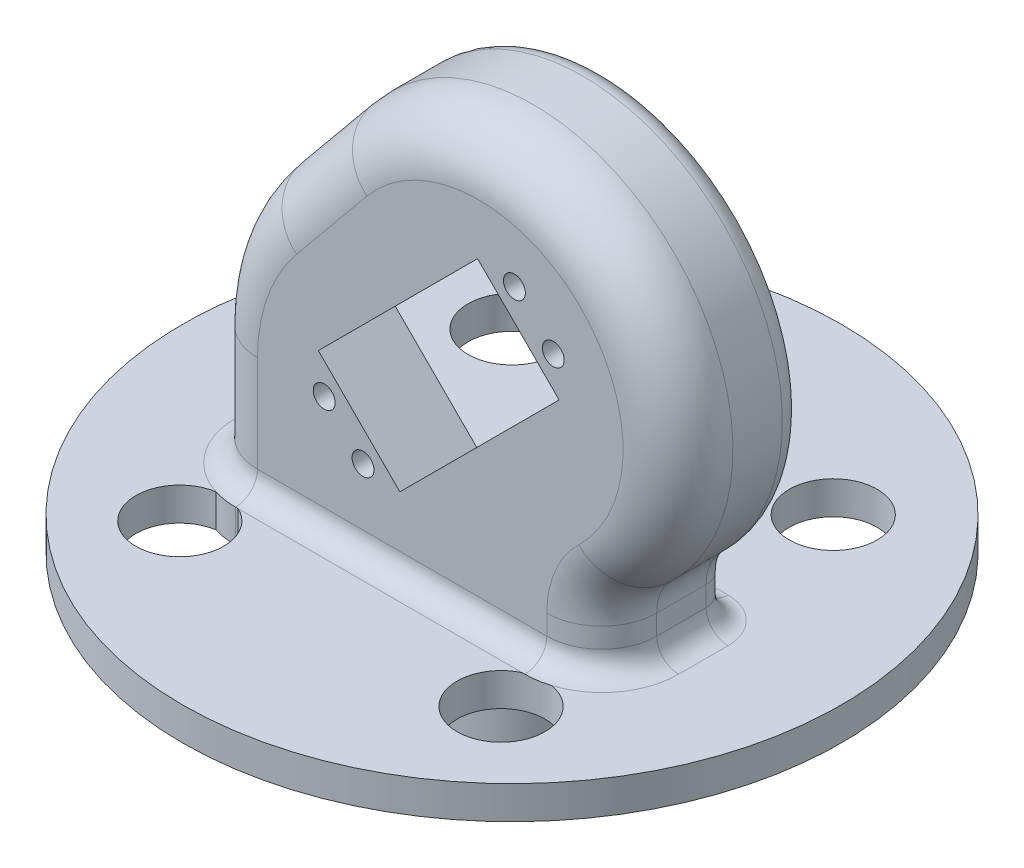
SolidWorks part; units mm, degrees
ref_plane "Front Plane" through (0, 0, 0) normal (0, 0, 1) x (1, 0, 0)
ref_plane "Top Plane" through (0, 0, 0) normal (0, 1, 0) x (1, 0, 0)
ref_plane "Right Plane" through (0, 0, 0) normal (1, 0, 0) x (0, 0, -1)
sketch "Sketch1" plane through (0, 0, 0) normal (0, 1, 0) x (1, 0, 0)
  line L0 (0, -7.25) -> (0, 7.25)
  circle A0 centre (0, 0) radius 60
  circle A1 centre (0, 7.25) radius 1.5
  circle A2 centre (0, -7.25) radius 1.5
  point P6 (0, 0)
  dimension "D2" = 120
  dimension "D3" = 3
  dimension "D1" = 14.5
extrude "Boss-Extrude2" add sketch "Sketch1" along normal blind 4 contours A0 A2 A1 region at (-58.3029, 0, 0)
sketch "Sketch8" plane through (0, 0, 0) normal (0, 0, 1) x (1, 0, 0)
  line L0 (-30.34, 4) -> (30.34, 4)
  line L1 (-30.34, 4) -> (-30.34, 25.5686)
  line L2 (60, 4) -> (-60, 4) construction
  line L3 (30.34, 4) -> (30.34, 11.64)
  line L4 (-22.3212, 47.945) -> (-9.5029, 63.533)
  arc A0 (30.34, 11.64) -> (34.9356, 22.445) centre (45.34, 11.64) cw
  arc A1 (34.9356, 22.445) -> (-9.5029, 63.533) centre (13.91, 44.28) ccw
  arc A2 (-30.34, 25.5686) -> (-22.3212, 47.945) centre (4.89, 25.5686) cw
  circle A3 centre (13.91, 44.28) radius 9
  point P2 (0, 4)
  dimension "D3" = 15
  dimension "D4" = 35.23
  dimension "D5" = 13.91
  dimension "D6" = 18
  dimension "D1" = 60.68
  dimension "D2" = 7.64
  dimension "D7" = 40.28
extrude "Boss-Extrude3" add sketch "Sketch8" along normal blind 14 from offset 6 contours A3 | A2 L1 L0 L3 A0 A1 L4 A3 region at (6.5155, 35.8962, 0) region at (13.91, 44.28, 0)
sketch "Sketch9" plane through (0, 0, 0) normal (0, -1, 0) x (1, 0, 0)
  arc A0 (0.8292, 6) -> (-0.8292, 6) centre (0, 7.25) ccw construction
  circle A1 centre (0, -7.25) radius 1.5
  circle A2 centre (0, -7.25) radius 1.5
  arc A3 (0.8292, 6) -> (-0.8292, 6) centre (0, 7.25) ccw
  circle M3 centre (0, -7.25) radius 1.5
  circle M4 centre (0, 7.25) radius 1.5
  dimension "D1" = 0
extrude "Boss-Extrude4" add sketch "Sketch9" against normal up to surface (4 mm away) contours M3 | M4 | A2 region at (0, 0, -7.25) region at (0, 0, 7.25) up to face at (0, 4, -5.75)
sketch "Sketch21" plane through (0, 0, 20) normal (0, 0, 1) x (1, 0, 0)
  line L1 (60, 4) -> (-60, 4) construction
  line L2 (36.34, 11.64) -> (36.34, 4)
  line L3 (36.34, 11.64) -> (36.34, 4)
  line L4 (-30.34, 4) -> (-27.34, 4)
  line L5 (-36.34, 4) -> (-27.34, 4)
  line L6 (30.34, 4) -> (36.34, 4)
  line L9 (-26.9556, 51.7559) -> (-14.1373, 67.3439)
  line L10 (-36.34, 4) -> (-36.34, 25.5686)
  line L11 (-26.9556, 51.7559) -> (-14.1373, 67.3439)
  line L12 (-36.34, 4) -> (-36.34, 25.5686)
  line L14 (33.34, 11.64) -> (33.34, 4)
  line L15 (-24.6384, 49.8505) -> (-11.8201, 65.4384)
  line L16 (-33.34, 4) -> (-33.34, 25.5686)
  line L17 (33.34, 11.64) -> (33.34, 4) construction
  line L18 (-24.6384, 49.8505) -> (-11.8201, 65.4384) construction
  line L19 (-33.34, 4) -> (-33.34, 25.5686) construction
  arc A2 (-9.5029, 63.533) -> (-27.34, 4) centre (72.6291, 6.4862) ccw
  arc A3 (39.0973, 18.123) -> (36.34, 11.64) centre (45.34, 11.64) ccw
  arc A4 (39.0973, 18.123) -> (36.34, 11.64) centre (45.34, 11.64) ccw
  arc A7 (39.0973, 18.123) -> (-14.1373, 67.3439) centre (13.91, 44.28) ccw
  arc A8 (-26.9556, 51.7559) -> (-36.34, 25.5686) centre (4.89, 25.5686) ccw
  arc A9 (39.0973, 18.123) -> (-14.1373, 67.3439) centre (13.91, 44.28) ccw
  arc A10 (-26.9556, 51.7559) -> (-36.34, 25.5686) centre (4.89, 25.5686) ccw
  arc A13 (37.0165, 20.284) -> (33.34, 11.64) centre (45.34, 11.64) ccw
  arc A14 (37.0165, 20.284) -> (-11.8201, 65.4384) centre (13.91, 44.28) ccw
  arc A15 (-24.6384, 49.8505) -> (-33.34, 25.5686) centre (4.89, 25.5686) ccw
  arc A16 (37.0165, 20.284) -> (33.34, 11.64) centre (45.34, 11.64) ccw construction
  arc A17 (37.0165, 20.284) -> (-11.8201, 65.4384) centre (13.91, 44.28) ccw construction
  arc A18 (-24.6384, 49.8505) -> (-33.34, 25.5686) centre (4.89, 25.5686) ccw construction
  arc M22 (-22.3212, 47.945) -> (-30.34, 25.5686) centre (4.89, 25.5686) ccw
  line M23 (-30.34, 25.5686) -> (-30.34, 4)
  line M24 (-30.34, 4) -> (30.34, 4)
  line M25 (30.34, 4) -> (30.34, 11.64)
  arc M26 (30.34, 11.64) -> (34.9356, 22.445) centre (45.34, 11.64) cw
  arc M27 (34.9356, 22.445) -> (-9.5029, 63.533) centre (13.91, 44.28) ccw
  line M28 (-9.5029, 63.533) -> (-22.3212, 47.945)
  dimension "D5" = 100
  dimension "D4" = 3
  dimension "D1" = 3
  dimension "D2" = 6
  dimension "D3" = 6
extrude "Boss-Extrude8" add sketch "Sketch21" against normal blind 23 contours A2 M28 M22 M23 M24 | L11 A10 L12 L5 L6 L3 A4 A9 M23 M22 M28 M27 M26 M25 region at (35.1842, 7.82, 20) region at (31.84, 5.0912, 20) region at (-25.4241, 31.3052, 20)
sketch "Sketch35" plane through (0, 0, 20) normal (0, 0, 1) x (1, 0, 0)
  line L0 (-15.2592, 32.227) -> (13.7321, 61.2184)
  line L1 (-15.2592, 32.227) -> (-0.41, 17.3778)
  line L2 (13.7321, 61.2184) -> (28.5814, 46.3692)
  line L3 (-0.41, 17.3778) -> (28.5814, 46.3692)
  line L4 (-36.34, 4) -> (36.34, 4) construction
  line L5 (21.1568, 53.7938) -> (-7.8346, 24.8024) construction
  line L6 (-0.7636, 46.7227) -> (14.0857, 31.8735) construction
  line L7 (10.1966, 50.2582) -> (17.4444, 57.5061) construction
  line L8 (21.1568, 53.7938) -> (13.7321, 61.2184) construction
  line L9 (17.4444, 57.5061) -> (-11.5469, 28.5147) construction
  line L10 (10.1966, 50.2582) -> (2.9488, 43.0104) construction
  line L11 (23.9781, 56.6151) -> (27.5136, 53.0796) construction
  line L12 (21.1568, 53.7938) -> (23.9781, 56.6151) construction
  line L13 (20.4426, 60.1507) -> (27.5136, 53.0796) construction
  circle A0 centre (20.4426, 60.1507) radius 1.6
  circle A1 centre (27.5136, 53.0796) radius 1.6
  circle A2 centre (-7.1204, 18.4455) radius 1.6
  circle A3 centre (-14.1915, 25.5166) radius 1.6
  point P21 (23.9781, 56.6151)
  dimension "D7" = 3.2
  dimension "D1" = 0.41
  dimension "D2" = 21
  dimension "D3" = 41
  dimension "D4" = 45
  dimension "D5" = 3.99
  dimension "D6" = 10
extrude "Cut-Extrude6" cut sketch "Sketch35" against normal up to surface (14 mm away) up to face at (14.9403, 26.211, 6)
fillet "Fillet1" radius 10 6 edges at (36.34, 7.82, 20) (37.058, 15.1625, 20) (-36.34, 14.7843, 20) (-33.923, 39.4776, 20) (-20.5464, 59.5499, 20) (38.5619, 70.9422, 20)
fillet "Fillet2" radius 4 6 edges at (36.34, 7.82, -3) (37.058, 15.1625, -3) (-36.34, 14.7843, -3) (-33.923, 39.4776, -3) (-20.5464, 59.5499, -3) (38.5619, 70.9422, -3)
fillet "Fillet3" radius 4 9 edges at (31.34, 4, -3) (35.1684, 4, -1.8284) (36.34, 4, 5.5) (33.4111, 4, 17.0711) (0, 4, 20) (-33.4111, 4, 17.0711) (-36.34, 4, 5.5) (-29.84, 4, -3) (-35.1684, 4, -1.8284)
sketch "Sketch40" plane through (0, 0, 0) normal (0, -1, 0) x (1, 0, 0)
  circle A1 centre (0, 0) radius 60
  circle A2 centre (0, 0) radius 60
  dimension "D1" = 0
extrude "Boss-Extrude9" add sketch "Sketch40" along normal blind 2
sketch "Sketch42" plane through (0, 0, 20) normal (0, 0, 1) x (1, 0, 0)
  line L4 (-26.34, 25.5686) -> (-26.34, 8)
  line L5 (-26.34, 8) -> (26.34, 8)
  line L6 (26.34, 8) -> (26.34, 11.64)
  line L7 (-6.4134, 60.9923) -> (-19.2317, 45.4044)
  line L8 (-26.34, 25.5686) -> (-26.34, 8)
  line L9 (-26.34, 8) -> (26.34, 8)
  line L10 (26.34, 8) -> (26.34, 11.64)
  line L11 (-6.4134, 60.9923) -> (-19.2317, 45.4044)
  circle A0 centre (20.4426, 60.1507) radius 1.6 construction
  circle A1 centre (20.4426, 60.1507) radius 1.6
  circle A2 centre (20.4426, 60.1507) radius 1.995
  arc A3 (32.161, 25.3263) -> (26.34, 11.64) centre (45.34, 11.64) ccw
  arc A4 (32.161, 25.3263) -> (-6.4134, 60.9923) centre (13.91, 44.28) ccw
  arc A5 (-19.2317, 45.4044) -> (-26.34, 25.5686) centre (4.89, 25.5686) ccw
  arc A6 (32.161, 25.3263) -> (26.34, 11.64) centre (45.34, 11.64) ccw
  arc A7 (32.161, 25.3263) -> (-6.4134, 60.9923) centre (13.91, 44.28) ccw
  arc A8 (-19.2317, 45.4044) -> (-26.34, 25.5686) centre (4.89, 25.5686) ccw
  circle A9 centre (27.5136, 53.0796) radius 1.995
  circle A10 centre (-14.1915, 25.5166) radius 1.995
  circle A11 centre (-7.1204, 18.4455) radius 1.995
  circle M16 centre (-14.1915, 25.5166) radius 1.6
  circle M17 centre (-7.1204, 18.4455) radius 1.6
  circle M18 centre (27.5136, 53.0796) radius 1.6
  circle M19 centre (20.4426, 60.1507) radius 1.6
  dimension "D2" = 3.99
  dimension "D1" = 0
extrude "Cut-Extrude7" cut sketch "Sketch42" against normal up to surface (14 mm away) contours A2 M19 | A9 M18 | A10 M16 | A11 M17 region at (18.504, 60.1507, 20) region at (25.5751, 53.0796, 20) region at (-16.1301, 25.5166, 20) region at (-9.059, 18.4455, 20) up to face at (-12.5915, 25.5166, 6)
sketch "Sketch43" plane through (0, 0, 0) normal (1, 0, 0) x (0, 0, -1)
  line L0 (60, 4) -> (60, -1.5) construction
  line L1 (60, -2) -> (60, 4) construction
sketch "Sketch44" plane through (0, -2, 0) normal (0, -1, 0) x (1, 0, 0)
  circle A0 centre (0, 0) radius 12.5
  dimension "D1" = 25
extrude "Boss-Extrude10" add sketch "Sketch44" along normal blind 16
sketch "Sketch46" plane through (0, -18, 0) normal (0, -1, 0) x (1, 0, 0)
  circle A0 centre (0, 0) radius 1
  dimension "D1" = 2
extrude "Cut-Extrude8" cut sketch "Sketch46" against normal up to surface (22 mm away) up to face at (0.5, 4, 4.7071)
sketch "Sketch47" plane through (0, -18, 0) normal (0, -1, 0) x (1, 0, 0)
  circle A0 centre (0, 0) radius 1.5
  dimension "D1" = 3
extrude "Cut-Extrude9" cut sketch "Sketch47" against normal up to surface (22 mm away) up to face at (0, 4, 1)
sketch "Sketch51" plane through (0, -18, 0) normal (0, -1, 0) x (1, 0, 0)
  line L0 (0, 0) -> (-7.5, 0) construction
  line L1 (0, 0) -> (0, 7.5) construction
  circle A0 centre (-7.5, 0) radius 0.75
  circle A1 centre (-7.5, 3.2) radius 0.75
  circle A2 centre (7.5, 0) radius 0.75
  circle A3 centre (7.5, 3.2) radius 0.75
  circle A4 centre (0, 7.5) radius 0.75
  circle A5 centre (3.2, 7.5) radius 0.75
  circle A6 centre (-3.2, 7.5) radius 0.75
  circle A7 centre (3.2, -7.5) radius 0.75
  circle A8 centre (0, -7.5) radius 0.75
  circle A9 centre (-3.2, -7.5) radius 0.75
  circle A10 centre (7.5, -3.2) radius 0.75
  circle A11 centre (-7.5, -3.2) radius 0.75
  dimension "D3" = 1.5
  dimension "D5" = 1.5
  dimension "D6" = 2
  dimension "D1" = 7.5
  dimension "D2" = 7.5
  dimension "D4" = 2
extrude "Cut-Extrude11" cut sketch "Sketch51" against normal blind 13.5
sketch "Sketch53" plane through (0, -18, 0) normal (0, -1, 0) x (1, 0, 0)
  circle A0 centre (0, 0) radius 10.5
  dimension "D1" = 21
extrude "Cut-Extrude13" cut sketch "Sketch53" against normal blind 2.5
sketch "Sketch55" plane through (0, 4, 0) normal (0, 1, 0) x (1, 0, 0)
  circle A0 centre (0, 0) radius 2.1
  dimension "D1" = 4.2
extrude "Cut-Extrude14" cut sketch "Sketch55" against normal offset from surface (18.5 mm away) 1 up to face at (0, -15.5, -10.5)
sketch "Sketch56" plane through (0, -15.5, 0) normal (0, -1, 0) x (1, 0, 0)
  circle A0 centre (0, 0) radius 1.25
  circle M15 centre (0, 0) radius 1.5
  dimension "D1" = 2.5
extrude "Boss-Extrude12" add sketch "Sketch56" against normal up to surface (1 mm away) contours A0 M15 region at (-1.4576, -15.5, 0) up to face at (0, -14.5, -2.1)
sketch "Sketch57" plane through (0, -15.5, 0) normal (0, -1, 0) x (1, 0, 0)
  circle A0 centre (0, 0) radius 4.625
  dimension "D1" = 9.25
extrude "Cut-Extrude15" cut sketch "Sketch57" against normal blind 0.8 contours A0
sketch "Sketch58" plane through (0, -2, 0) normal (0, -1, 0) x (1, 0, 0)
  circle A0 centre (0, 0) radius 15.635
  dimension "D1" = 31.27
extrude "Boss-Extrude13" add sketch "Sketch58" along normal blind 4
sketch "Sketch59" plane through (0, -18, 0) normal (0, -1, 0) x (1, 0, 0)
  line L0 (0, 15.635) -> (0, -12.5)
  line L1 (-12.5, 0) -> (12.5, 0)
  line L2 (-8.42, -4) -> (-8.42, 4)
  line L3 (-17.1, 0) -> (-12.5, 0) construction
  line L4 (-17.1, 0) -> (-17.9, 0) construction
  line L5 (-17.9, 0) -> (-20, 0) construction
  line L6 (-17.9, 0) -> (-17.9, 2.4678) construction
  line L7 (-17.9, 2.4678) -> (-17.9, -2.4678) construction
  line L8 (-17.9, 2.4678) -> (-8.42, 4)
  line L9 (-17.9, -2.4678) -> (-8.42, -4)
  line L10 (-8.42, 4) -> (-5.5, 4)
  line L11 (-5.5, 4) -> (-5.5, 5.5) construction
  line L12 (-4, 5.5) -> (-4, 8.42)
  line L13 (0, 17.1) -> (0, 20) construction
  line L14 (-4, 8.42) -> (4, 8.42)
  line L15 (0, 17.1) -> (0, 17.9) construction
  line L17 (0, 20) -> (0, 17.5) construction
  line L18 (-2.465, 17.9) -> (-4, 8.42)
  line L19 (2.465, 17.9) -> (4, 8.42)
  line L20 (-8.42, -4) -> (-5.5, -4)
  line L21 (-4, -5.5) -> (-4, -8.42)
  line L22 (2.465, -17.9) -> (4, -8.42)
  line L23 (-2.465, -17.9) -> (-4, -8.42)
  line L24 (4, -5.5) -> (4, -8.42)
  line L25 (8.42, -4) -> (5.5, -4)
  line L26 (8.42, 4) -> (5.5, 4)
  line L27 (4, 5.5) -> (4, 8.42)
  line L28 (17.9, -2.4678) -> (8.42, -4)
  line L29 (17.9, 2.4678) -> (8.42, 4)
  line L30 (-2.9586, -17.9799) -> (-4.5, -8.4602)
  line L31 (-4.5, -5.5) -> (-4.5, -8.4602)
  line L32 (-8.4601, -4.5) -> (-5.5, -4.5)
  line L33 (-17.9799, -2.9614) -> (-8.4601, -4.5)
  line L34 (-17.9799, 2.9614) -> (-8.4601, 4.5)
  line L35 (-8.4601, 4.5) -> (-5.5, 4.5)
  line L36 (-4.5, 5.5) -> (-4.5, 8.4602)
  line L37 (-2.9586, 17.9799) -> (-4.5, 8.4602)
  line L38 (2.9586, 17.9799) -> (4.5, 8.4602)
  line L39 (4.5, 5.5) -> (4.5, 8.4602)
  line L40 (8.4601, 4.5) -> (5.5, 4.5)
  line L41 (17.9799, 2.9614) -> (8.4601, 4.5)
  line L42 (17.9799, -2.9614) -> (8.4601, -4.5)
  line L43 (8.4601, -4.5) -> (5.5, -4.5)
  line L44 (4.5, -5.5) -> (4.5, -8.4602)
  line L45 (2.9586, -17.9799) -> (4.5, -8.4602)
  circle A0 centre (-7.5, 0) radius 0.75
  circle A1 centre (-10.7, 0) radius 0.75
  circle A2 centre (-13.9, 0) radius 0.75
  circle A3 centre (-17.1, 0) radius 0.75
  circle A4 centre (0, 0) radius 15.635 construction
  circle A5 centre (0, 0) radius 15.635 construction
  circle A6 centre (0, 0) radius 12.5 construction
  circle A7 centre (0, 0) radius 12.5 construction
  circle A8 centre (10.7, 0) radius 0.75
  circle A9 centre (7.5, 0) radius 0.75
  circle A10 centre (17.1, 0) radius 0.75
  circle A11 centre (13.9, 0) radius 0.75
  circle A12 centre (0, -7.5) radius 0.75
  circle A13 centre (0, -10.7) radius 0.75
  circle A14 centre (0, -13.9) radius 0.75
  circle A15 centre (0, -17.1) radius 0.75
  circle A16 centre (0, 7.5) radius 0.75
  circle A17 centre (0, 10.7) radius 0.75
  circle A18 centre (0, 13.9) radius 0.75
  circle A19 centre (0, 17.1) radius 0.75
  arc A21 (-17.9, 2.4678) -> (-17.9, -2.4678) centre (-17.5, 0) ccw
  arc A22 (-5.5, 4) -> (-4, 5.5) centre (-5.5, 5.5) ccw
  arc A24 (2.4839, 17.7833) -> (-2.4839, 17.7833) centre (0, 17.5) ccw
  arc A25 (-5.5, -4) -> (-4, -5.5) centre (-5.5, -5.5) cw
  arc A26 (2.4839, -17.7833) -> (-2.4839, -17.7833) centre (0, -17.5) cw
  arc A27 (5.5, -4) -> (4, -5.5) centre (5.5, -5.5) ccw
  arc A28 (5.5, 4) -> (4, 5.5) centre (5.5, 5.5) cw
  arc A29 (17.9, 2.4678) -> (17.9, -2.4678) centre (17.5, 0) cw
  arc A30 (-5.5, -4.5) -> (-4.5, -5.5) centre (-5.5, -5.5) cw
  arc A31 (-17.9799, 2.9614) -> (-17.9799, -2.9614) centre (-17.5, 0) ccw
  arc A32 (-5.5, 4.5) -> (-4.5, 5.5) centre (-5.5, 5.5) ccw
  arc A33 (5.5, 4.5) -> (4.5, 5.5) centre (5.5, 5.5) cw
  arc A34 (17.9799, 2.9614) -> (17.9799, -2.9614) centre (17.5, 0) cw
  arc A35 (5.5, -4.5) -> (4.5, -5.5) centre (5.5, -5.5) ccw
  arc A36 (2.9807, -17.84) -> (-2.9807, -17.84) centre (0, -17.5) cw
  arc A37 (2.9807, 17.84) -> (-2.9807, 17.84) centre (0, 17.5) ccw
  point P50 (-8.42, 0)
  point P68 (0, 17.9)
  circle M10 centre (0, 0) radius 10.5
  circle M11 centre (0, 0) radius 12.5
  dimension "D12" = 2.5
  dimension "D3" = 8
  dimension "D4" = 0.92
  dimension "D5" = 0.8
  dimension "D6" = 2.1
  dimension "D7" = 2.92
  dimension "D8" = 0.5
  dimension "D9" = 2.92
  dimension "D10" = 2.9
  dimension "D11" = 8
  dimension "D13" = 0.8
  dimension "D14" = 4.93
  dimension "D15" = 0.5
  dimension "D1" = 4
  dimension "D2" = 4
extrude "Cut-Extrude16" cut sketch "Sketch59" against normal up to surface (2.5 mm away) contours L45 L22 M11 M10 | A35 L43 L42 L28 L25 A27 L24 L22 L45 L44 M10 | L42 L28 M11 M10 | A34 L41 L29 A29 L28 L42 M11 | L41 L29 M11 M10 | L40 A33 L39 L38 L19 L27 A28 L26 L29 L41 M10 | A37 L37 L18 A24 L19 L38 | L38 L19 M11 M10 | L37 L18 M11 M10 | A32 L35 L34 L8 L10 A22 L12 L18 L37 L36 M10 | L32 A30 L31 L30 L23 L21 A25 L20 L9 L33 M10 | L30 L23 M11 M10 | L34 A31 L33 L9 A21 L8 M11 | L33 L9 M11 M10 | L34 L8 M11 M10 | L8 A21 L9 A3 A2 M11 | A26 L22 L23 A14 A15 M11 | A36 L45 L22 A26 L23 L30 | A13 L0 L22 M11 M10 | A13 L23 L0 M10 M11 | A27 L25 L28 A8 L1 A9 L0 A12 A13 L22 L24 M10 | L20 A25 L21 L23 A13 L0 A12 L1 A0 L2 M10 | A22 L10 L2 L1 A0 L0 A16 L14 L12 | L0 A17 L19 M10 M11 | A17 L0 L18 M10 M11 | L0 A17 L18 L14 M10 | A17 L0 L14 L19 M10 | L26 A28 L27 L14 L0 A16 L1 A9 A8 L29 M10 | A29 L29 L28 A10 A11 M11 | A8 L1 L29 M10 M11 | L1 A8 L28 M10 M11 | A24 L18 A18 L19 A19 M11 | A1 L1 L2 L8 M10 | A1 L8 L1 M10 M11 | A1 L9 L2 L1 M10 | A1 L1 L9 M11 M10 region at (0, -18, 15.7387) region at (1.9464, -18, 11.3202) region at (-1.9464, -18, 11.3202) region at (3.8666, -18, 10.815) region at (3.0657, -18, 14.9224) region at (-3.8666, -18, 10.815) region at (-1.8786, -18, 9.3073) region at (4.0174, -18, 9.6088) region at (1.8786, -18, 9.3073) region at (-3.9725, -18, 9.1222) region at (4.1474, -18, 3.2535) region at (10.8148, -18, 3.8674) region at (14.9009, -18, 3.3404) region at (-3.4415, -18, 3.4415) region at (-12.0564, -18, 3.7195) region at (-10.8148, -18, 3.8674) region at (11.3202, -18, 1.9468) region at (15.7385, -18, 0) region at (-15.7385, -18, 0) region at (-11.3202, -18, 1.9468) region at (11.3202, -18, -1.9468) region at (-9.3073, -18, 1.8787) region at (-11.3202, -18, -1.9468) region at (10.8148, -18, -3.8674) region at (-10.8148, -18, -3.8674) region at (3.9037, -18, -3.9037) region at (-3.2535, -18, -4.1473) region at (9.0014, -18, -4.3263) region at (3.8666, -18, -10.815) region at (3.3488, -18, -14.8372) region at (-9.3073, -18, -1.8787) region at (-9.6087, -18, -4.0178) region at (-3.8666, -18, -10.815) region at (1.9464, -18, -11.3202) region at (0, -18, -15.7387) region at (-1.9464, -18, -11.3202) up to face at (0, -15.5, -4.625)
sketch "Sketch60" plane through (0, -15.5, 0) normal (0, -1, 0) x (1, 0, 0)
  circle A0 centre (0, 10.7) radius 0.75
  circle A1 centre (0, -10.7) radius 0.75
  circle A2 centre (10.7, 0) radius 0.75
  circle A3 centre (-10.7, 0) radius 0.7575
extrude "Cut-Extrude18" cut sketch "Sketch60" along normal through all and the other way up to surface (9.5 mm away) other way up to face at (-7.5, -6, -0.75)
sketch "Sketch61" plane through (0, -18, 0) normal (0, -1, 0) x (1, 0, 0)
  line L0 (3.9496, 11.8596) -> (4.3203, 9.57) construction
  line L1 (9.5699, 4.3206) -> (11.8593, 3.9506) construction
  line L2 (11.8593, -3.9506) -> (9.5699, -4.3206) construction
  line L3 (4.3203, -9.57) -> (3.9496, -11.8596) construction
  line L4 (-3.9496, -11.8596) -> (-4.3203, -9.57) construction
  line L5 (-9.5699, -4.3206) -> (-11.8593, -3.9506) construction
  line L6 (-11.8593, 3.9506) -> (-9.5699, 4.3206) construction
  line L7 (-4.3203, 9.57) -> (-3.9496, 11.8596) construction
  line L8 (3.9496, 11.8596) -> (4.3203, 9.57)
  line L9 (9.5699, 4.3206) -> (11.8593, 3.9506)
  line L10 (11.8593, -3.9506) -> (9.5699, -4.3206)
  line L11 (4.3203, -9.57) -> (3.9496, -11.8596)
  line L12 (-3.9496, -11.8596) -> (-4.3203, -9.57)
  line L13 (-9.5699, -4.3206) -> (-11.8593, -3.9506)
  line L14 (-11.8593, 3.9506) -> (-9.5699, 4.3206)
  line L15 (-4.3203, 9.57) -> (-3.9496, 11.8596)
  arc A0 (11.8593, 3.9506) -> (3.9496, 11.8596) centre (0, 0) ccw construction
  arc A1 (9.5699, 4.3206) -> (4.3203, 9.57) centre (0, 0) ccw construction
  arc A2 (3.9496, -11.8596) -> (11.8593, -3.9506) centre (0, 0) ccw construction
  arc A3 (4.3203, -9.57) -> (9.5699, -4.3206) centre (0, 0) ccw construction
  arc A4 (-11.8593, -3.9506) -> (-3.9496, -11.8596) centre (0, 0) ccw construction
  arc A5 (-9.5699, -4.3206) -> (-4.3203, -9.57) centre (0, 0) ccw construction
  arc A6 (-3.9496, 11.8596) -> (-11.8593, 3.9506) centre (0, 0) ccw construction
  arc A7 (-4.3203, 9.57) -> (-9.5699, 4.3206) centre (0, 0) ccw construction
  arc A8 (4.3203, -9.57) -> (9.5699, -4.3206) centre (0, 0) ccw construction
  arc A9 (11.8593, 3.9506) -> (3.9496, 11.8596) centre (0, 0) ccw
  arc A10 (9.5699, 4.3206) -> (4.3203, 9.57) centre (0, 0) ccw
  arc A11 (3.9496, -11.8596) -> (11.8593, -3.9506) centre (0, 0) ccw
  arc A12 (4.3203, -9.57) -> (9.5699, -4.3206) centre (0, 0) ccw
  arc A13 (-11.8593, -3.9506) -> (-3.9496, -11.8596) centre (0, 0) ccw
  arc A14 (-9.5699, -4.3206) -> (-4.3203, -9.57) centre (0, 0) ccw
  arc A15 (-3.9496, 11.8596) -> (-11.8593, 3.9506) centre (0, 0) ccw
  arc A16 (-4.3203, 9.57) -> (-9.5699, 4.3206) centre (0, 0) ccw
  arc A17 (4.3203, -9.57) -> (9.5699, -4.3206) centre (0, 0) ccw
  arc M1 (-3.9496, 11.8596) -> (-11.8593, 3.9506) centre (0, 0) ccw
  line M2 (-11.8593, 3.9506) -> (-9.5699, 4.3206)
  arc M3 (-9.5699, 4.3206) -> (-4.3203, 9.57) centre (0, 0) cw
  line M4 (-4.3203, 9.57) -> (-3.9496, 11.8596)
extrude "Boss-Extrude14" add sketch "Sketch61" along normal blind 2.5 contours M4 M1 M2 M3 | A10 L9 A9 L8 | A12 L11 A11 L10 | A14 L12 A13 L13 region at (7.9399, -18, 7.9405) region at (7.9399, -18, -7.9405) region at (-7.9399, -18, 7.9405)
sketch "Sketch62" plane through (0, -15.5, 0) normal (0, -1, 0) x (1, 0, 0)
  line L8 (-4.3203, -9.57) -> (-3.9496, -11.8596)
  line L9 (3.9496, -11.8596) -> (4.3203, -9.57)
  line L10 (9.5699, -4.3206) -> (11.8593, -3.9506)
  line L11 (11.8593, 3.9506) -> (9.5699, 4.3206)
  line L12 (4.3203, 9.57) -> (3.9496, 11.8596)
  line L13 (-3.9496, 11.8596) -> (-4.3203, 9.57)
  line L14 (-9.5699, 4.3206) -> (-11.8593, 3.9506)
  line L15 (-11.8593, -3.9506) -> (-9.5699, -4.3206)
  line L16 (-4.3203, -9.57) -> (-3.9496, -11.8596)
  line L17 (3.9496, -11.8596) -> (4.3203, -9.57)
  line L18 (9.5699, -4.3206) -> (11.8593, -3.9506)
  line L19 (11.8593, 3.9506) -> (9.5699, 4.3206)
  line L20 (4.3203, 9.57) -> (3.9496, 11.8596)
  line L21 (-3.9496, 11.8596) -> (-4.3203, 9.57)
  line L22 (-9.5699, 4.3206) -> (-11.8593, 3.9506)
  line L23 (-11.8593, -3.9506) -> (-9.5699, -4.3206)
  circle A0 centre (-7.5, 0) radius 0.75 construction
  circle A1 centre (-7.5, 0) radius 0.75
  circle A2 centre (-10.7, 0) radius 0.7575 construction
  circle A3 centre (-10.7, 0) radius 0.7575
  circle A4 centre (-3.2, 7.5) radius 0.75 construction
  circle A5 centre (0, 7.5) radius 0.75 construction
  circle A6 centre (3.2, 7.5) radius 0.75 construction
  circle A7 centre (7.5, 3.2) radius 0.75 construction
  arc A8 (-9.5699, -4.3206) -> (-4.3203, -9.57) centre (0, 0) ccw
  arc A9 (-3.9496, -11.8596) -> (3.9496, -11.8596) centre (0, 0) ccw
  arc A10 (4.3203, -9.57) -> (9.5699, -4.3206) centre (0, 0) ccw
  arc A11 (11.8593, -3.9506) -> (11.8593, 3.9506) centre (0, 0) ccw
  arc A12 (9.5699, 4.3206) -> (4.3203, 9.57) centre (0, 0) ccw
  arc A13 (3.9496, 11.8596) -> (-3.9496, 11.8596) centre (0, 0) ccw
  arc A14 (-4.3203, 9.57) -> (-9.5699, 4.3206) centre (0, 0) ccw
  arc A15 (-11.8593, 3.9506) -> (-11.8593, -3.9506) centre (0, 0) ccw
  arc A16 (-9.5699, -4.3206) -> (-4.3203, -9.57) centre (0, 0) ccw
  arc A17 (-3.9496, -11.8596) -> (3.9496, -11.8596) centre (0, 0) ccw
  arc A18 (4.3203, -9.57) -> (9.5699, -4.3206) centre (0, 0) ccw
  arc A19 (11.8593, -3.9506) -> (11.8593, 3.9506) centre (0, 0) ccw
  arc A20 (9.5699, 4.3206) -> (4.3203, 9.57) centre (0, 0) ccw
  arc A21 (3.9496, 11.8596) -> (-3.9496, 11.8596) centre (0, 0) ccw
  arc A22 (-4.3203, 9.57) -> (-9.5699, 4.3206) centre (0, 0) ccw
  arc A23 (-11.8593, 3.9506) -> (-11.8593, -3.9506) centre (0, 0) ccw
  circle A24 centre (7.5, 0) radius 0.75 construction
  circle A25 centre (7.5, -3.2) radius 0.75 construction
  circle A26 centre (3.2, -7.5) radius 0.75 construction
  circle A27 centre (0, -10.7) radius 0.75 construction
  circle A28 centre (0, -7.5) radius 0.75 construction
  circle A29 centre (-3.2, -7.5) radius 0.75 construction
  circle A30 centre (-7.5, -3.2) radius 0.75 construction
  circle A31 centre (-7.5, 3.2) radius 0.75 construction
  circle A32 centre (-3.2, 7.5) radius 0.75
  circle A33 centre (0, 7.5) radius 0.75
  circle A34 centre (3.2, 7.5) radius 0.75
  circle A35 centre (7.5, 3.2) radius 0.75
  circle A36 centre (7.5, 0) radius 0.75
  circle A37 centre (7.5, -3.2) radius 0.75
  circle A38 centre (3.2, -7.5) radius 0.75
  circle A39 centre (0, -10.7) radius 0.75
  circle A40 centre (0, -7.5) radius 0.75
  circle A41 centre (-3.2, -7.5) radius 0.75
  circle A42 centre (-7.5, -3.2) radius 0.75
  circle A43 centre (-7.5, 3.2) radius 0.75
  circle M17 centre (-10.7, 0) radius 0.7575
  arc M18 (-9.5699, -4.3206) -> (-4.3203, -9.57) centre (0, 0) ccw
  line M19 (-4.3203, -9.57) -> (-3.9496, -11.8596)
  arc M20 (-3.9496, -11.8596) -> (3.9496, -11.8596) centre (0, 0) ccw
  line M21 (3.9496, -11.8596) -> (4.3203, -9.57)
  arc M22 (4.3203, -9.57) -> (9.5699, -4.3206) centre (0, 0) ccw
  line M23 (9.5699, -4.3206) -> (11.8593, -3.9506)
  arc M24 (11.8593, -3.9506) -> (11.8593, 3.9506) centre (0, 0) ccw
  line M25 (11.8593, 3.9506) -> (9.5699, 4.3206)
  arc M26 (9.5699, 4.3206) -> (4.3203, 9.57) centre (0, 0) ccw
  line M27 (4.3203, 9.57) -> (3.9496, 11.8596)
  arc M28 (3.9496, 11.8596) -> (-3.9496, 11.8596) centre (0, 0) ccw
  line M29 (-3.9496, 11.8596) -> (-4.3203, 9.57)
  arc M30 (-4.3203, 9.57) -> (-9.5699, 4.3206) centre (0, 0) ccw
  line M31 (-9.5699, 4.3206) -> (-11.8593, 3.9506)
  arc M32 (-11.8593, 3.9506) -> (-11.8593, -3.9506) centre (0, 0) ccw
  line M33 (-11.8593, -3.9506) -> (-9.5699, -4.3206)
  circle M34 centre (0, 10.7) radius 0.75
  circle M35 centre (10.7, 0) radius 0.75
  circle M36 centre (0, -10.7) radius 0.75
  circle M37 centre (0, 0) radius 4.625
  circle M38 centre (0, -7.5) radius 0.75
  circle M39 centre (3.2, -7.5) radius 0.75
  circle M40 centre (-3.2, 7.5) radius 0.75
  circle M41 centre (3.2, 7.5) radius 0.75
  circle M42 centre (-7.5, 3.2) radius 0.75
  circle M43 centre (7.5, 0) radius 0.75
  circle M44 centre (7.5, 3.2) radius 0.75
  circle M45 centre (0, 7.5) radius 0.75
  circle M46 centre (-3.2, -7.5) radius 0.75
  circle M47 centre (7.5, -3.2) radius 0.75
  circle M48 centre (-7.5, -3.2) radius 0.75
  circle M49 centre (-7.5, 0) radius 0.75
  dimension "D1" = 0
extrude "Boss-Extrude17" add sketch "Sketch62" along normal blind 2.5 contours M33 M18 M19 M20 M21 M22 M23 M24 M25 M26 M27 M28 M29 M30 M31 M32 M35 M37 M39 M41 M43 M45 M47 M49 M48 M46 M44 M42 M40 M38 M36 M34 M17 region at (-7.1745, -15.5, -7.1747)
sketch "Sketch63" plane through (0, -14.7, 0) normal (0, -1, 0) x (1, 0, 0)
  circle A0 centre (0, 0) radius 1.25 construction
  circle A1 centre (0, 0) radius 4.625
  circle A2 centre (0, 0) radius 4.625
  circle A3 centre (0, 0) radius 1.25
  circle M2 centre (0, 0) radius 4.625
  circle M3 centre (0, 0) radius 1.25
  dimension "D1" = 0
extrude "Boss-Extrude20" add sketch "Sketch63" along normal blind 2.5 contours M2 M3 region at (-4.4942, -14.7, 0)
sketch "Sketch64" plane through (0, -20.5, 0) normal (0, -1, 0) x (1, 0, 0)
  circle A0 centre (0, 0) radius 12.5
  circle A1 centre (0, 0) radius 12
  dimension "D1" = 24
extrude "Cut-Extrude19" cut sketch "Sketch64" against normal up to surface (14.5 mm away) up to face at (0, -6, -15.635)
sketch "Sketch69" plane through (0, -2, 0) normal (0, -1, 0) x (1, 0, 0)
  circle A0 centre (0, 0) radius 57.5
  circle A1 centre (0, 0) radius 60
  circle A2 centre (0, 0) radius 60
  dimension "D2" = 115
  dimension "D1" = 0
sketch "Sketch70" plane through (0, -2, 0) normal (0, -1, 0) x (1, 0, 0)
  line L0 (-20, 59.991) -> (-20, -59.991)
  line L1 (-20, 59.991) -> (20, 59.991)
  line L2 (-60, 19.991) -> (-60, -19.991)
  line L3 (-20, -59.991) -> (20, -59.991)
  line L4 (60, 19.991) -> (60, -19.991)
  line L5 (-20, 19.997) -> (20, -19.997) construction
  line L6 (-20, -19.997) -> (20, 19.997) construction
  line L7 (20, 59.991) -> (20, -59.991)
  line L8 (-60, 19.991) -> (60, 19.991)
  line L9 (-60, -19.991) -> (60, -19.991)
  point P0 (0, 0)
  dimension "D2" = 40
  dimension "D3" = 40
  dimension "D4" = 40
  dimension "D5" = 40
sketch "Sketch72" plane through (0, -20.5, 0) normal (0, -1, 0) x (1, 0, 0)
  line L0 (4.3203, -9.57) -> (4.0403, -11.2994) construction
  line L1 (11.2991, -4.0412) -> (9.5699, -4.3206) construction
  line L2 (9.5699, 4.3206) -> (11.2991, 4.0412) construction
  line L3 (4.0403, 11.2994) -> (4.3203, 9.57) construction
  line L4 (-9.5699, -4.3206) -> (-11.2991, -4.0412) construction
  line L5 (-4.0403, -11.2994) -> (-4.3203, -9.57) construction
  line L6 (-4.3203, 9.57) -> (-4.0403, 11.2994) construction
  line L7 (-11.2991, 4.0412) -> (-9.5699, 4.3206) construction
  line L8 (4.3203, -9.57) -> (4.0403, -11.2994)
  line L9 (11.2991, -4.0412) -> (9.5699, -4.3206)
  line L10 (9.5699, 4.3206) -> (11.2991, 4.0412)
  line L11 (4.0403, 11.2994) -> (4.3203, 9.57)
  line L12 (-9.5699, -4.3206) -> (-11.2991, -4.0412)
  line L13 (-4.0403, -11.2994) -> (-4.3203, -9.57)
  line L14 (-4.3203, 9.57) -> (-4.0403, 11.2994)
  line L15 (-11.2991, 4.0412) -> (-9.5699, 4.3206)
  arc A0 (4.0403, -11.2994) -> (11.2991, -4.0412) centre (0, 0) ccw construction
  arc A1 (4.3203, -9.57) -> (9.5699, -4.3206) centre (0, 0) ccw construction
  arc A2 (11.2991, 4.0412) -> (4.0403, 11.2994) centre (0, 0) ccw construction
  arc A3 (9.5699, 4.3206) -> (4.3203, 9.57) centre (0, 0) ccw construction
  arc A4 (-11.2991, -4.0412) -> (-4.0403, -11.2994) centre (0, 0) ccw construction
  arc A5 (-9.5699, -4.3206) -> (-4.3203, -9.57) centre (0, 0) ccw construction
  arc A6 (-4.0403, 11.2994) -> (-11.2991, 4.0412) centre (0, 0) ccw construction
  arc A7 (-4.3203, 9.57) -> (-9.5699, 4.3206) centre (0, 0) ccw construction
  arc A8 (4.0403, -11.2994) -> (11.2991, -4.0412) centre (0, 0) ccw
  arc A9 (4.3203, -9.57) -> (9.5699, -4.3206) centre (0, 0) ccw
  arc A10 (11.2991, 4.0412) -> (4.0403, 11.2994) centre (0, 0) ccw
  arc A11 (9.5699, 4.3206) -> (4.3203, 9.57) centre (0, 0) ccw
  arc A12 (-11.2991, -4.0412) -> (-4.0403, -11.2994) centre (0, 0) ccw
  arc A13 (-9.5699, -4.3206) -> (-4.3203, -9.57) centre (0, 0) ccw
  arc A14 (-4.0403, 11.2994) -> (-11.2991, 4.0412) centre (0, 0) ccw
  arc A15 (-4.3203, 9.57) -> (-9.5699, 4.3206) centre (0, 0) ccw
extrude "Boss-Extrude21" add sketch "Sketch72" along normal blind 7
sketch "Sketch73" plane through (0, -18, 0) normal (0, -1, 0) x (1, 0, 0)
  line L8 (9.5699, -4.3206) -> (11.2991, -4.0412)
  line L9 (11.2991, 4.0412) -> (9.5699, 4.3206)
  line L10 (4.3203, 9.57) -> (4.0403, 11.2994)
  line L11 (-4.0403, 11.2994) -> (-4.3203, 9.57)
  line L12 (-9.5699, 4.3206) -> (-11.2991, 4.0412)
  line L13 (-11.2991, -4.0412) -> (-9.5699, -4.3206)
  line L14 (-4.3203, -9.57) -> (-4.0403, -11.2994)
  line L15 (4.0403, -11.2994) -> (4.3203, -9.57)
  line L16 (9.5699, -4.3206) -> (11.2991, -4.0412)
  line L17 (11.2991, 4.0412) -> (9.5699, 4.3206)
  line L18 (4.3203, 9.57) -> (4.0403, 11.2994)
  line L19 (-4.0403, 11.2994) -> (-4.3203, 9.57)
  line L20 (-9.5699, 4.3206) -> (-11.2991, 4.0412)
  line L21 (-11.2991, -4.0412) -> (-9.5699, -4.3206)
  line L22 (-4.3203, -9.57) -> (-4.0403, -11.2994)
  line L23 (4.0403, -11.2994) -> (4.3203, -9.57)
  arc A8 (11.2991, -4.0412) -> (11.2991, 4.0412) centre (0, 0) ccw
  arc A9 (9.5699, 4.3206) -> (4.3203, 9.57) centre (0, 0) ccw
  arc A10 (4.0403, 11.2994) -> (-4.0403, 11.2994) centre (0, 0) ccw
  arc A11 (-4.3203, 9.57) -> (-9.5699, 4.3206) centre (0, 0) ccw
  arc A12 (-11.2991, 4.0412) -> (-11.2991, -4.0412) centre (0, 0) ccw
  arc A13 (-9.5699, -4.3206) -> (-4.3203, -9.57) centre (0, 0) ccw
  arc A14 (-4.0403, -11.2994) -> (4.0403, -11.2994) centre (0, 0) ccw
  arc A15 (4.3203, -9.57) -> (9.5699, -4.3206) centre (0, 0) ccw
  arc A16 (11.2991, -4.0412) -> (11.2991, 4.0412) centre (0, 0) ccw
  arc A17 (9.5699, 4.3206) -> (4.3203, 9.57) centre (0, 0) ccw
  arc A18 (4.0403, 11.2994) -> (-4.0403, 11.2994) centre (0, 0) ccw
  arc A19 (-4.3203, 9.57) -> (-9.5699, 4.3206) centre (0, 0) ccw
  arc A20 (-11.2991, 4.0412) -> (-11.2991, -4.0412) centre (0, 0) ccw
  arc A21 (-9.5699, -4.3206) -> (-4.3203, -9.57) centre (0, 0) ccw
  arc A22 (-4.0403, -11.2994) -> (4.0403, -11.2994) centre (0, 0) ccw
  arc A23 (4.3203, -9.57) -> (9.5699, -4.3206) centre (0, 0) ccw
  circle M17 centre (10.7, 0) radius 0.75
  circle M18 centre (0, 0) radius 4.625
  circle M19 centre (3.2, -7.5) radius 0.75
  circle M20 centre (3.2, 7.5) radius 0.75
  circle M21 centre (7.5, 0) radius 0.75
  circle M22 centre (0, 7.5) radius 0.75
  circle M23 centre (7.5, -3.2) radius 0.75
  circle M24 centre (-7.5, 0) radius 0.75
  circle M25 centre (-7.5, -3.2) radius 0.75
  circle M26 centre (-3.2, -7.5) radius 0.75
  circle M27 centre (7.5, 3.2) radius 0.75
  circle M28 centre (-7.5, 3.2) radius 0.75
  circle M29 centre (-3.2, 7.5) radius 0.75
  circle M30 centre (0, -7.5) radius 0.75
  circle M31 centre (0, -10.7) radius 0.75
  circle M32 centre (0, 10.7) radius 0.75
  circle M33 centre (-10.7, 0) radius 0.7575
  line M34 (9.5699, -4.3206) -> (11.2991, -4.0412)
  arc M35 (11.2991, -4.0412) -> (11.2991, 4.0412) centre (0, 0) ccw
  line M36 (11.2991, 4.0412) -> (9.5699, 4.3206)
  arc M37 (9.5699, 4.3206) -> (4.3203, 9.57) centre (0, 0) ccw
  line M38 (4.3203, 9.57) -> (4.0403, 11.2994)
  arc M39 (4.0403, 11.2994) -> (-4.0403, 11.2994) centre (0, 0) ccw
  line M40 (-4.0403, 11.2994) -> (-4.3203, 9.57)
  arc M41 (-4.3203, 9.57) -> (-9.5699, 4.3206) centre (0, 0) ccw
  line M42 (-9.5699, 4.3206) -> (-11.2991, 4.0412)
  arc M43 (-11.2991, 4.0412) -> (-11.2991, -4.0412) centre (0, 0) ccw
  line M44 (-11.2991, -4.0412) -> (-9.5699, -4.3206)
  arc M45 (-9.5699, -4.3206) -> (-4.3203, -9.57) centre (0, 0) ccw
  line M46 (-4.3203, -9.57) -> (-4.0403, -11.2994)
  arc M47 (-4.0403, -11.2994) -> (4.0403, -11.2994) centre (0, 0) ccw
  line M48 (4.0403, -11.2994) -> (4.3203, -9.57)
  arc M49 (4.3203, -9.57) -> (9.5699, -4.3206) centre (0, 0) ccw
  dimension "D1" = 0
extrude "Boss-Extrude22" add sketch "Sketch73" along normal blind 7 contours M49 M34 M35 M36 M37 M38 M39 M40 M41 M42 M43 M44 M45 M46 M47 M48 M18 M20 M22 M24 M26 M28 M30 M32 M33 M31 M29 M27 M25 M23 M21 M19 M17 region at (7.1845, -18, -7.1847)
sketch "Sketch74" plane through (0, -17.2, 0) normal (0, -1, 0) x (1, 0, 0)
  circle A0 centre (0, 0) radius 1.25 construction
  circle A1 centre (0, 0) radius 4.625
  circle A2 centre (0, 0) radius 4.625
  circle A3 centre (0, 0) radius 1.25
  circle M2 centre (0, 0) radius 1.25
  circle M3 centre (0, 0) radius 4.625
  dimension "D1" = 0
extrude "Boss-Extrude24" add sketch "Sketch74" along normal blind 7 contours M3 M2 region at (-4.4942, -17.2, 0)
sketch "Sketch76" plane through (0, 4, 0) normal (0, 1, 0) x (1, 0, 0)
  line L0 (0, 38.4887) -> (0, -38.4887)
  line L1 (-38.4887, 38.4887) -> (38.4887, 38.4887)
  line L2 (-38.4887, 38.4887) -> (-38.4887, -38.4887)
  line L3 (-38.4887, -38.4887) -> (38.4887, -38.4887)
  line L4 (38.4887, 38.4887) -> (38.4887, -38.4887)
  line L5 (-38.4887, 38.4887) -> (38.4887, -38.4887) construction
  line L6 (-38.4887, -38.4887) -> (38.4887, 38.4887) construction
  line L7 (-60, 19.991) -> (60, 19.991)
  line L8 (-20, 59.991) -> (-20, -59.991)
  line L9 (-38.34, -1) -> (38.4887, -1)
  line L10 (-36.34, -1) -> (-40.34, -1) construction
  line L11 (50.2224, -1) -> (-14.1373, -1) construction
  line L12 (-38.4887, 38.4887) -> (-20, 38.4887) construction
  line L13 (-20, 38.4887) -> (-38.4887, 38.4887) construction
  line L14 (-20, 19.997) -> (-38.4887, 19.991) construction
  line L15 (-38.4887, 19.991) -> (-38.4887, 38.4887) construction
  line L16 (-38.4887, 19.991) -> (-20, 38.4887) construction
  circle A0 centre (-29.2444, 29.2398) radius 8
  circle A1 centre (29.2444, 29.2398) radius 8
  circle A2 centre (29.2444, -31.2398) radius 8
  circle A3 centre (-29.2444, -31.2398) radius 8
  point P1 (0, 0)
  arc M14 (40.34, -10) -> (26.34, -24) centre (26.34, -10) cw
  line M15 (26.34, -24) -> (-26.34, -24)
  arc M16 (-26.34, -24) -> (-40.34, -10) centre (-26.34, -10) cw
  dimension "D1" = 16
extrude "Cut-Extrude20" cut sketch "Sketch76" against normal up to surface (6 mm away) contours A1 | A0 | A3 L3 M15 M16 | A3 L3 | L3 A2 M14 M15 | L3 A2 | A2 region at (29.2539, 4, 31.1775) region at (29.2444, 4, 38.7904) region at (-29.2539, 4, 31.1775) region at (-29.2444, 4, 38.7904) region at (-29.2444, 4, -29.2398) region at (29.2444, 4, -29.2398) up to face at (0, -2, -15.635)
sketch "Sketch78" plane through (0, -27.5, 0) normal (0, -1, 0) x (1, 0, 0)
  line L0 (-9.5699, -4.3206) -> (-11.2991, -4.0412) construction
  line L1 (-4.0403, -11.2994) -> (-4.3203, -9.57) construction
  line L2 (-4.3203, 9.57) -> (-4.0403, 11.2994)
  line L3 (-11.2991, 4.0412) -> (-9.5699, 4.3206)
  line L4 (-4.3203, 9.57) -> (-4.0403, 11.2994)
  line L5 (-11.2991, 4.0412) -> (-9.5699, 4.3206)
  line L6 (4.3203, -9.57) -> (4.0403, -11.2994) construction
  line L7 (11.2991, -4.0412) -> (9.5699, -4.3206) construction
  line L8 (9.5699, 4.3206) -> (11.2991, 4.0412) construction
  line L9 (4.0403, 11.2994) -> (4.3203, 9.57) construction
  line L10 (-9.5699, -4.3206) -> (-11.2991, -4.0412)
  line L11 (-4.0403, -11.2994) -> (-4.3203, -9.57)
  line L12 (4.3203, -9.57) -> (4.0403, -11.2994)
  line L13 (11.2991, -4.0412) -> (9.5699, -4.3206)
  line L14 (9.5699, 4.3206) -> (11.2991, 4.0412)
  line L15 (4.0403, 11.2994) -> (4.3203, 9.57)
  arc A0 (-9.5699, -4.3206) -> (-4.3203, -9.57) centre (0, 0) ccw construction
  arc A1 (-11.2991, -4.0412) -> (-4.0403, -11.2994) centre (0, 0) ccw construction
  arc A2 (-4.3203, 9.57) -> (-9.5699, 4.3206) centre (0, 0) ccw
  arc A3 (-4.0403, 11.2994) -> (-11.2991, 4.0412) centre (0, 0) ccw
  arc A4 (-4.3203, 9.57) -> (-9.5699, 4.3206) centre (0, 0) ccw
  arc A5 (-4.0403, 11.2994) -> (-11.2991, 4.0412) centre (0, 0) ccw
  arc A6 (4.3203, -9.57) -> (9.5699, -4.3206) centre (0, 0) ccw construction
  arc A7 (4.0403, -11.2994) -> (11.2991, -4.0412) centre (0, 0) ccw construction
  arc A8 (9.5699, 4.3206) -> (4.3203, 9.57) centre (0, 0) ccw construction
  arc A9 (11.2991, 4.0412) -> (4.0403, 11.2994) centre (0, 0) ccw construction
  arc A10 (-9.5699, -4.3206) -> (-4.3203, -9.57) centre (0, 0) ccw
  arc A11 (-11.2991, -4.0412) -> (-4.0403, -11.2994) centre (0, 0) ccw
  arc A12 (4.3203, -9.57) -> (9.5699, -4.3206) centre (0, 0) ccw
  arc A13 (4.0403, -11.2994) -> (11.2991, -4.0412) centre (0, 0) ccw
  arc A14 (9.5699, 4.3206) -> (4.3203, 9.57) centre (0, 0) ccw
  arc A15 (11.2991, 4.0412) -> (4.0403, 11.2994) centre (0, 0) ccw
  dimension "D1" = 0
extrude "Boss-Extrude25" add sketch "Sketch78" along normal blind 5.65
sketch "Sketch80" plane through (0, -25, 0) normal (0, -1, 0) x (1, 0, 0)
  line L8 (9.5699, -4.3206) -> (11.2991, -4.0412)
  line L9 (11.2991, 4.0412) -> (9.5699, 4.3206)
  line L10 (4.3203, 9.57) -> (4.0403, 11.2994)
  line L11 (-4.0403, 11.2994) -> (-4.3203, 9.57)
  line L12 (-9.5699, 4.3206) -> (-11.2991, 4.0412)
  line L13 (-11.2991, -4.0412) -> (-9.5699, -4.3206)
  line L14 (-4.3203, -9.57) -> (-4.0403, -11.2994)
  line L15 (4.0403, -11.2994) -> (4.3203, -9.57)
  line L16 (9.5699, -4.3206) -> (11.2991, -4.0412)
  line L17 (11.2991, 4.0412) -> (9.5699, 4.3206)
  line L18 (4.3203, 9.57) -> (4.0403, 11.2994)
  line L19 (-4.0403, 11.2994) -> (-4.3203, 9.57)
  line L20 (-9.5699, 4.3206) -> (-11.2991, 4.0412)
  line L21 (-11.2991, -4.0412) -> (-9.5699, -4.3206)
  line L22 (-4.3203, -9.57) -> (-4.0403, -11.2994)
  line L23 (4.0403, -11.2994) -> (4.3203, -9.57)
  arc A8 (4.3203, -9.57) -> (9.5699, -4.3206) centre (0, 0) ccw
  arc A9 (11.2991, -4.0412) -> (11.2991, 4.0412) centre (0, 0) ccw
  arc A10 (9.5699, 4.3206) -> (4.3203, 9.57) centre (0, 0) ccw
  arc A11 (4.0403, 11.2994) -> (-4.0403, 11.2994) centre (0, 0) ccw
  arc A12 (-4.3203, 9.57) -> (-9.5699, 4.3206) centre (0, 0) ccw
  arc A13 (-11.2991, 4.0412) -> (-11.2991, -4.0412) centre (0, 0) ccw
  arc A14 (-9.5699, -4.3206) -> (-4.3203, -9.57) centre (0, 0) ccw
  arc A15 (-4.0403, -11.2994) -> (4.0403, -11.2994) centre (0, 0) ccw
  arc A16 (4.3203, -9.57) -> (9.5699, -4.3206) centre (0, 0) ccw
  arc A17 (11.2991, -4.0412) -> (11.2991, 4.0412) centre (0, 0) ccw
  arc A18 (9.5699, 4.3206) -> (4.3203, 9.57) centre (0, 0) ccw
  arc A19 (4.0403, 11.2994) -> (-4.0403, 11.2994) centre (0, 0) ccw
  arc A20 (-4.3203, 9.57) -> (-9.5699, 4.3206) centre (0, 0) ccw
  arc A21 (-11.2991, 4.0412) -> (-11.2991, -4.0412) centre (0, 0) ccw
  arc A22 (-9.5699, -4.3206) -> (-4.3203, -9.57) centre (0, 0) ccw
  arc A23 (-4.0403, -11.2994) -> (4.0403, -11.2994) centre (0, 0) ccw
  circle M17 centre (0, 0) radius 4.625
  circle M18 centre (3.2, 7.5) radius 0.75
  circle M19 centre (0, 7.5) radius 0.75
  circle M20 centre (-7.5, 0) radius 0.75
  circle M21 centre (-3.2, -7.5) radius 0.75
  circle M22 centre (-7.5, 3.2) radius 0.75
  circle M23 centre (0, -7.5) radius 0.75
  circle M24 centre (0, 10.7) radius 0.75
  arc M25 (4.3203, -9.57) -> (9.5699, -4.3206) centre (0, 0) ccw
  line M26 (9.5699, -4.3206) -> (11.2991, -4.0412)
  arc M27 (11.2991, -4.0412) -> (11.2991, 4.0412) centre (0, 0) ccw
  line M28 (11.2991, 4.0412) -> (9.5699, 4.3206)
  arc M29 (9.5699, 4.3206) -> (4.3203, 9.57) centre (0, 0) ccw
  line M30 (4.3203, 9.57) -> (4.0403, 11.2994)
  arc M31 (4.0403, 11.2994) -> (-4.0403, 11.2994) centre (0, 0) ccw
  line M32 (-4.0403, 11.2994) -> (-4.3203, 9.57)
  arc M33 (-4.3203, 9.57) -> (-9.5699, 4.3206) centre (0, 0) ccw
  line M34 (-9.5699, 4.3206) -> (-11.2991, 4.0412)
  arc M35 (-11.2991, 4.0412) -> (-11.2991, -4.0412) centre (0, 0) ccw
  line M36 (-11.2991, -4.0412) -> (-9.5699, -4.3206)
  arc M37 (-9.5699, -4.3206) -> (-4.3203, -9.57) centre (0, 0) ccw
  line M38 (-4.3203, -9.57) -> (-4.0403, -11.2994)
  arc M39 (-4.0403, -11.2994) -> (4.0403, -11.2994) centre (0, 0) ccw
  line M40 (4.0403, -11.2994) -> (4.3203, -9.57)
  circle M41 centre (-10.7, 0) radius 0.7575
  circle M42 centre (0, -10.7) radius 0.75
  circle M43 centre (-3.2, 7.5) radius 0.75
  circle M44 centre (7.5, 3.2) radius 0.75
  circle M45 centre (-7.5, -3.2) radius 0.75
  circle M46 centre (7.5, -3.2) radius 0.75
  circle M47 centre (7.5, 0) radius 0.75
  circle M48 centre (3.2, -7.5) radius 0.75
  circle M49 centre (10.7, 0) radius 0.75
  dimension "D1" = 0
extrude "Boss-Extrude26" add sketch "Sketch80" along normal blind 5.65 contours M40 M25 M26 M27 M28 M29 M30 M31 M32 M33 M34 M35 M36 M37 M38 M39 M18 M20 M22 M24 M41 M43 M45 M47 M49 M48 M46 M44 M42 M23 M21 M19 M17 region at (7.1845, -25, -7.1847)
sketch "Sketch81" plane through (0, -24.2, 0) normal (0, -1, 0) x (1, 0, 0)
  circle A0 centre (0, 0) radius 1.25 construction
  circle A1 centre (0, 0) radius 4.625
  circle A2 centre (0, 0) radius 4.625
  circle A3 centre (0, 0) radius 1.25
  dimension "D1" = 0
extrude "Boss-Extrude27" add sketch "Sketch81" along normal blind 5.65
sketch "Sketch82" plane through (0, -33.15, 0) normal (0, -1, 0) x (1, 0, 0)
  line L2 (-9.5699, -4.3206) -> (-11.2991, -4.0412)
  line L3 (-4.0403, -11.2994) -> (-4.3203, -9.57)
  line L4 (-9.5699, -4.3206) -> (-11.2991, -4.0412)
  line L5 (-4.0403, -11.2994) -> (-4.3203, -9.57)
  line L6 (-4.3203, 9.57) -> (-4.0403, 11.2994)
  line L7 (-11.2991, 4.0412) -> (-9.5699, 4.3206)
  line L8 (-4.3203, 9.57) -> (-4.0403, 11.2994)
  line L9 (-11.2991, 4.0412) -> (-9.5699, 4.3206)
  line L12 (9.5699, 4.3206) -> (11.2991, 4.0412)
  line L13 (4.0403, 11.2994) -> (4.3203, 9.57)
  line L14 (9.5699, 4.3206) -> (11.2991, 4.0412)
  line L15 (4.0403, 11.2994) -> (4.3203, 9.57)
  line L16 (4.3203, -9.57) -> (4.0403, -11.2994)
  line L17 (11.2991, -4.0412) -> (9.5699, -4.3206)
  line L18 (4.3203, -9.57) -> (4.0403, -11.2994)
  line L19 (11.2991, -4.0412) -> (9.5699, -4.3206)
  arc A2 (-9.5699, -4.3206) -> (-4.3203, -9.57) centre (0, 0) ccw
  arc A3 (-11.2991, -4.0412) -> (-4.0403, -11.2994) centre (0, 0) ccw
  arc A4 (-9.5699, -4.3206) -> (-4.3203, -9.57) centre (0, 0) ccw
  arc A5 (-11.2991, -4.0412) -> (-4.0403, -11.2994) centre (0, 0) ccw
  arc A6 (-4.3203, 9.57) -> (-9.5699, 4.3206) centre (0, 0) ccw
  arc A7 (-4.0403, 11.2994) -> (-11.2991, 4.0412) centre (0, 0) ccw
  arc A8 (-4.3203, 9.57) -> (-9.5699, 4.3206) centre (0, 0) ccw
  arc A9 (-4.0403, 11.2994) -> (-11.2991, 4.0412) centre (0, 0) ccw
  arc A12 (9.5699, 4.3206) -> (4.3203, 9.57) centre (0, 0) ccw
  arc A13 (11.2991, 4.0412) -> (4.0403, 11.2994) centre (0, 0) ccw
  arc A14 (9.5699, 4.3206) -> (4.3203, 9.57) centre (0, 0) ccw
  arc A15 (11.2991, 4.0412) -> (4.0403, 11.2994) centre (0, 0) ccw
  arc A16 (4.3203, -9.57) -> (9.5699, -4.3206) centre (0, 0) ccw
  arc A17 (4.0403, -11.2994) -> (11.2991, -4.0412) centre (0, 0) ccw
  arc A18 (4.3203, -9.57) -> (9.5699, -4.3206) centre (0, 0) ccw
  arc A19 (4.0403, -11.2994) -> (11.2991, -4.0412) centre (0, 0) ccw
  dimension "D1" = 0
  dimension "D2" = 0
  dimension "D3" = 0
  dimension "D4" = 0
extrude "Cut-Extrude21" cut sketch "Sketch82" against normal blind 7
sketch "Sketch83" plane through (0, -30.65, 0) normal (0, -1, 0) x (1, 0, 0)
  line L8 (4.0403, -11.2994) -> (4.3203, -9.57)
  line L9 (9.5699, -4.3206) -> (11.2991, -4.0412)
  line L10 (11.2991, 4.0412) -> (9.5699, 4.3206)
  line L11 (4.3203, 9.57) -> (4.0403, 11.2994)
  line L12 (-4.0403, 11.2994) -> (-4.3203, 9.57)
  line L13 (-9.5699, 4.3206) -> (-11.2991, 4.0412)
  line L14 (-11.2991, -4.0412) -> (-9.5699, -4.3206)
  line L15 (-4.3203, -9.57) -> (-4.0403, -11.2994)
  line L16 (4.0403, -11.2994) -> (4.3203, -9.57)
  line L17 (9.5699, -4.3206) -> (11.2991, -4.0412)
  line L18 (11.2991, 4.0412) -> (9.5699, 4.3206)
  line L19 (4.3203, 9.57) -> (4.0403, 11.2994)
  line L20 (-4.0403, 11.2994) -> (-4.3203, 9.57)
  line L21 (-9.5699, 4.3206) -> (-11.2991, 4.0412)
  line L22 (-11.2991, -4.0412) -> (-9.5699, -4.3206)
  line L23 (-4.3203, -9.57) -> (-4.0403, -11.2994)
  arc A8 (4.3203, -9.57) -> (9.5699, -4.3206) centre (0, 0) ccw
  arc A9 (11.2991, -4.0412) -> (11.2991, 4.0412) centre (0, 0) ccw
  arc A10 (9.5699, 4.3206) -> (4.3203, 9.57) centre (0, 0) ccw
  arc A11 (4.0403, 11.2994) -> (-4.0403, 11.2994) centre (0, 0) ccw
  arc A12 (-4.3203, 9.57) -> (-9.5699, 4.3206) centre (0, 0) ccw
  arc A13 (-11.2991, 4.0412) -> (-11.2991, -4.0412) centre (0, 0) ccw
  arc A14 (-9.5699, -4.3206) -> (-4.3203, -9.57) centre (0, 0) ccw
  arc A15 (-4.0403, -11.2994) -> (4.0403, -11.2994) centre (0, 0) ccw
  arc A16 (4.3203, -9.57) -> (9.5699, -4.3206) centre (0, 0) ccw
  arc A17 (11.2991, -4.0412) -> (11.2991, 4.0412) centre (0, 0) ccw
  arc A18 (9.5699, 4.3206) -> (4.3203, 9.57) centre (0, 0) ccw
  arc A19 (4.0403, 11.2994) -> (-4.0403, 11.2994) centre (0, 0) ccw
  arc A20 (-4.3203, 9.57) -> (-9.5699, 4.3206) centre (0, 0) ccw
  arc A21 (-11.2991, 4.0412) -> (-11.2991, -4.0412) centre (0, 0) ccw
  arc A22 (-9.5699, -4.3206) -> (-4.3203, -9.57) centre (0, 0) ccw
  arc A23 (-4.0403, -11.2994) -> (4.0403, -11.2994) centre (0, 0) ccw
  circle M17 centre (3.2, 7.5) radius 0.75
  circle M18 centre (-7.5, 0) radius 0.75
  circle M19 centre (-7.5, 3.2) radius 0.75
  circle M20 centre (0, 10.7) radius 0.75
  circle M21 centre (-10.7, 0) radius 0.7575
  circle M22 centre (-3.2, 7.5) radius 0.75
  circle M23 centre (-7.5, -3.2) radius 0.75
  circle M24 centre (7.5, 0) radius 0.75
  circle M25 centre (10.7, 0) radius 0.75
  circle M26 centre (3.2, -7.5) radius 0.75
  circle M27 centre (7.5, -3.2) radius 0.75
  circle M28 centre (7.5, 3.2) radius 0.75
  circle M29 centre (0, -10.7) radius 0.75
  line M30 (4.0403, -11.2994) -> (4.3203, -9.57)
  arc M31 (4.3203, -9.57) -> (9.5699, -4.3206) centre (0, 0) ccw
  line M32 (9.5699, -4.3206) -> (11.2991, -4.0412)
  arc M33 (11.2991, -4.0412) -> (11.2991, 4.0412) centre (0, 0) ccw
  line M34 (11.2991, 4.0412) -> (9.5699, 4.3206)
  arc M35 (9.5699, 4.3206) -> (4.3203, 9.57) centre (0, 0) ccw
  line M36 (4.3203, 9.57) -> (4.0403, 11.2994)
  arc M37 (4.0403, 11.2994) -> (-4.0403, 11.2994) centre (0, 0) ccw
  line M38 (-4.0403, 11.2994) -> (-4.3203, 9.57)
  arc M39 (-4.3203, 9.57) -> (-9.5699, 4.3206) centre (0, 0) ccw
  line M40 (-9.5699, 4.3206) -> (-11.2991, 4.0412)
  arc M41 (-11.2991, 4.0412) -> (-11.2991, -4.0412) centre (0, 0) ccw
  line M42 (-11.2991, -4.0412) -> (-9.5699, -4.3206)
  arc M43 (-9.5699, -4.3206) -> (-4.3203, -9.57) centre (0, 0) ccw
  line M44 (-4.3203, -9.57) -> (-4.0403, -11.2994)
  arc M45 (-4.0403, -11.2994) -> (4.0403, -11.2994) centre (0, 0) ccw
  circle M46 centre (0, -7.5) radius 0.75
  circle M47 centre (-3.2, -7.5) radius 0.75
  circle M48 centre (0, 7.5) radius 0.75
  circle M49 centre (0, 0) radius 4.625
  dimension "D1" = 0
extrude "Cut-Extrude22" cut sketch "Sketch83" against normal blind 7 contours M45 M30 M31 M32 M33 M34 M35 M36 M37 M38 M39 M40 M41 M42 M43 M44 M18 M20 M22 M24 M26 M28 M47 M49 M48 M46 M29 M27 M25 M23 M21 M19 M17 region at (0, -30.65, -11.6606)
sketch "Sketch84" plane through (0, -29.85, 0) normal (0, -1, 0) x (1, 0, 0)
  circle A0 centre (0, 0) radius 1.25 construction
  circle A1 centre (0, 0) radius 4.625
  circle A2 centre (0, 0) radius 4.625
  circle A3 centre (0, 0) radius 1.25
  circle M2 centre (0, 0) radius 4.625
  circle M3 centre (0, 0) radius 1.25
  dimension "D1" = 0
extrude "Cut-Extrude23" cut sketch "Sketch84" against normal blind 7 contours M2 M3 | A2 region at (-4.4942, -29.85, 0)
